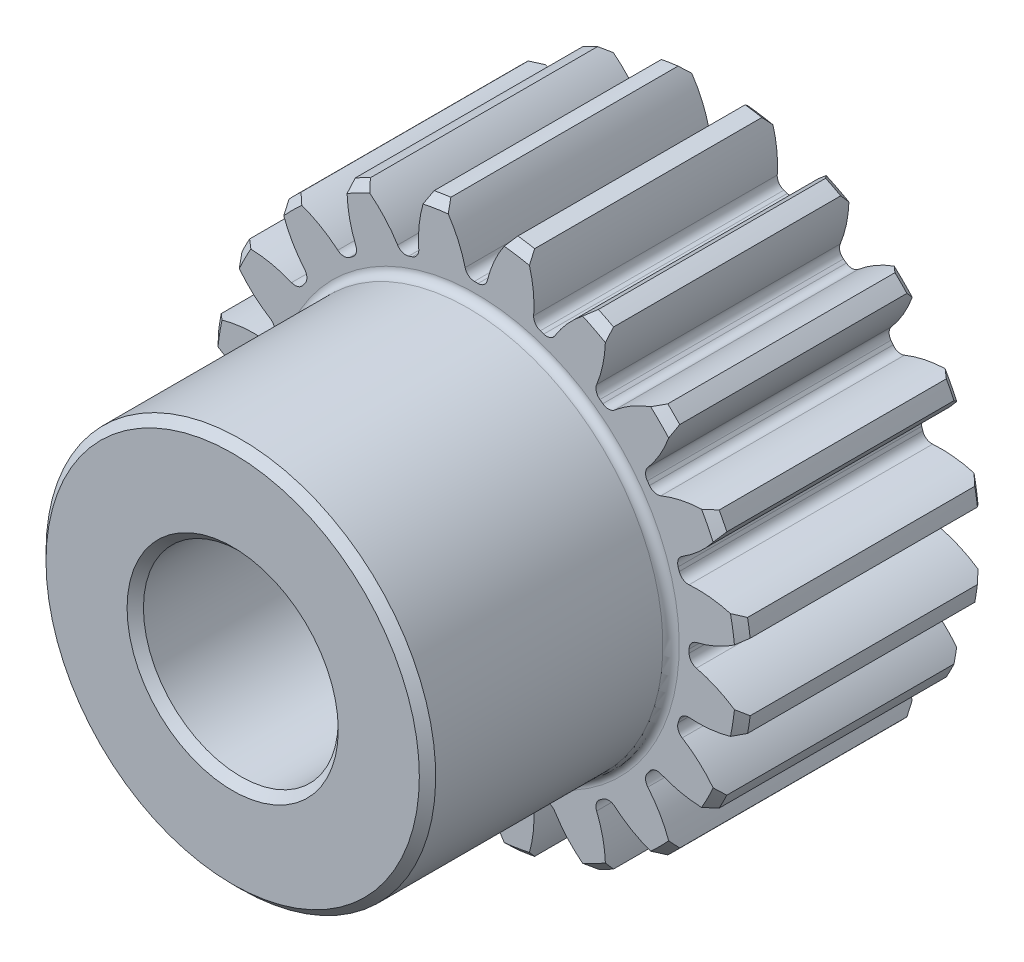
SolidWorks part; units mm, degrees
ref_plane "Front Plane" through (0, 0, 0) normal (0, 0, 1) x (1, 0, 0)
ref_plane "Top Plane" through (0, 0, 0) normal (0, 1, 0) x (1, 0, 0)
ref_plane "Right Plane" through (0, 0, 0) normal (1, 0, 0) x (0, 0, -1)
sketch "Sketch1" plane through (0, 0, 0) normal (0, 0, 1) x (1, 0, 0)
  line L0 (0, 0) -> (0, 10) construction
  line L1 (-3.2139, 11.1698) -> (3.2139, 8.8302) construction
  circle A0 centre (0, 0) radius 8.75 construction
  circle A1 centre (0, 0) radius 11 construction
  circle A2 centre (0, 0) radius 10 construction
  circle A3 centre (0, 0) radius 9.3969 construction
  circle A4 centre (0, 0) radius 8 construction
  circle A5 centre (0, 0) radius 4 construction
  point P8 (0.5, 0)
  point P13 (10, 0)
  dimension "OD" = 22
  dimension "Root Diameter" = 17.5
  dimension "Gear Pitch Diameter" = 20
  dimension "Base Diameter" = 18.7939
  dimension "Hub Diameter" = 16
  dimension "For Shaft Diameter" = 8
  dimension "Pressure Angle" = 20
  dimension "Number of Teeth" = 20
  dimension "Module" = 1
sketch "Sketch2" plane through (0, 0, 0) normal (1, 0, 0) x (0, 0, -1)
  line L0 (-10, 0) -> (10, 0) construction
  line L1 (10, 11) -> (10, -11) construction
  line L2 (0, -8) -> (-10, -8) construction
  line L3 (-10, 11) -> (10, 11) construction
  line L8 (-10, -8) -> (-10, 8) construction
  point P4 (0, 11)
  point P5 (-5, 0)
  dimension "Overall Width" = 20
  dimension "Hub Width" = 10
  dimension "Approx Set Screw Positon" = 5
  dimension "Face Width" = 10
sketch "Sketch3" plane through (0, 0, 0) normal (0, 0, 1) x (1, 0, 0)
  circle A0 centre (0, 0) radius 11
  circle A1 centre (0, 0) radius 11 construction
extrude "Boss-Extrude1" add sketch "Sketch3" against normal up to vertex (10 mm away) and the other way up to vertex (10 mm away) up to point (0, 0, -10) other way up to point (0, 0, 10)
sketch "Sketch5" plane through (0, 0, 0) normal (1, 0, 0) x (0, 0, -1)
  line L1 (0, 8) -> (-10, 8)
  line L2 (0, 8) -> (0, 11)
  line L3 (0, 11) -> (-10, 11)
  line L4 (-10, 8) -> (-10, 11)
  line L5 (-10, 0) -> (10, 0)
  line L6 (-10, 0) -> (-10, 4)
  line L7 (-10, 4) -> (10, 4)
  line L8 (10, 0) -> (10, 4)
  point P5 (0, 8)
  point P12 (0, 4)
revolve "Cut-Revolve1" cut sketch "Sketch5" angle 360 about L0
fillet "Fillet2" radius 0.3355 1 edges at (0, -8, 0)
chamfer "Chamfer1" distance 0.3355 angle 45 5 edges at (0, -4, -10) (0, -11, 0) (11, 0, -10) (0, -4, 10) (0, -8, 10)
sketch "Sketch4" plane through (0, 0, 0) normal (0, 0, 1) x (1, 0, 0)
  line L0 (8.7412, 0.3927) -> (8.7412, -0.3927)
  arc A3 (10.9135, 1.3768) -> (10.9135, -1.3768) centre (0, 0) cw
  circle A4 centre (0, 0) radius 11 construction
  arc A5 (8.7412, 0.3927) -> (10.9135, 1.3768) centre (7.8741, 5.1963) ccw
  circle A8 centre (0, 0) radius 8.75 construction
  arc A9 (8.7412, -0.3927) -> (10.9135, -1.3768) centre (7.8741, -5.1963) cw
  spline S0 degree 4 poles (9.3779, 0.5976) (9.3805, 0.5978) (9.3877, 0.5984) (9.4012, 0.6001) (9.4233, 0.6033) (9.4513, 0.6083) (9.4874, 0.6157) (9.5298, 0.6256) (9.5761, 0.6379) (9.6264, 0.6526) (9.6763, 0.6685) (9.7258, 0.6855) (9.775, 0.7034) (9.8343, 0.7264) (9.9051, 0.7556) (9.9872, 0.7922) (10.0797, 0.8366) (10.1732, 0.8848) (10.2645, 0.9348) (10.3559, 0.9882) (10.4438, 1.0418) (10.5341, 1.1004) (10.6171, 1.156) (10.709, 1.2214) (10.7829, 1.2752) (10.8792, 1.3494) (10.9357, 1.3943) (11.0014, 1.4479) (11.0304, 1.4723) (11.0482, 1.4873) knots 0 0 0 0 0 0.005377 0.015084 0.028532 0.04661 0.064855 0.092111 0.119476 0.146842 0.174209 0.201575 0.228941 0.256307 0.307035 0.361767 0.4165 0.471232 0.525964 0.580697 0.635429 0.690161 0.744894 0.799626 0.854358 0.909091 0.954545 1 1 1 1 1 construction
  spline S1 degree 4 poles (9.3779, 0.5976) (9.3805, 0.5978) (9.3877, 0.5984) (9.4012, 0.6001) (9.4233, 0.6033) (9.4513, 0.6083) (9.4874, 0.6157) (9.5298, 0.6256) (9.5761, 0.6379) (9.6264, 0.6526) (9.6763, 0.6685) (9.7258, 0.6855) (9.775, 0.7034) (9.8343, 0.7264) (9.9051, 0.7556) (9.9872, 0.7922) (10.0797, 0.8366) (10.1732, 0.8848) (10.2645, 0.9348) (10.3559, 0.9882) (10.4438, 1.0418) (10.5341, 1.1004) (10.6171, 1.156) (10.709, 1.2214) (10.7829, 1.2752) (10.8583, 1.3333) (10.8949, 1.362) (10.9135, 1.3768) knots 0 0 0 0 0 0.005377 0.015084 0.028532 0.04661 0.064855 0.092111 0.119476 0.146842 0.174209 0.201575 0.228941 0.256307 0.307035 0.361767 0.4165 0.471232 0.525964 0.580697 0.635429 0.690161 0.744894 0.799626 0.854358 0.909091 0.909091 0.909091 0.909091 0.909091 construction
  spline S2 degree 4 poles (9.3779, -0.5976) (9.3805, -0.5978) (9.3877, -0.5984) (9.4012, -0.6001) (9.4233, -0.6033) (9.4513, -0.6083) (9.4874, -0.6157) (9.5298, -0.6256) (9.5761, -0.6379) (9.6264, -0.6526) (9.6763, -0.6685) (9.7258, -0.6855) (9.775, -0.7034) (9.8343, -0.7264) (9.9051, -0.7556) (9.9872, -0.7922) (10.0797, -0.8366) (10.1732, -0.8848) (10.2645, -0.9348) (10.3559, -0.9882) (10.4438, -1.0418) (10.5341, -1.1004) (10.6171, -1.156) (10.709, -1.2214) (10.7829, -1.2752) (10.8792, -1.3494) (10.9357, -1.3943) (11.0014, -1.4479) (11.0304, -1.4723) (11.0482, -1.4873) knots 0 0 0 0 0 0.005377 0.015084 0.028532 0.04661 0.064855 0.092111 0.119476 0.146842 0.174209 0.201575 0.228941 0.256307 0.307035 0.361767 0.4165 0.471232 0.525964 0.580697 0.635429 0.690161 0.744894 0.799626 0.854358 0.909091 0.954545 1 1 1 1 1 construction
  spline S3 degree 4 poles (9.3779, -0.5976) (9.3805, -0.5978) (9.3877, -0.5984) (9.4012, -0.6001) (9.4233, -0.6033) (9.4513, -0.6083) (9.4874, -0.6157) (9.5298, -0.6256) (9.5761, -0.6379) (9.6264, -0.6526) (9.6763, -0.6685) (9.7258, -0.6855) (9.775, -0.7034) (9.8343, -0.7264) (9.9051, -0.7556) (9.9872, -0.7922) (10.0797, -0.8366) (10.1732, -0.8848) (10.2645, -0.9348) (10.3559, -0.9882) (10.4438, -1.0418) (10.5341, -1.1004) (10.6171, -1.156) (10.709, -1.2214) (10.7829, -1.2752) (10.8583, -1.3333) (10.8949, -1.362) (10.9135, -1.3768) knots 0 0 0 0 0 0.005377 0.015084 0.028532 0.04661 0.064855 0.092111 0.119476 0.146842 0.174209 0.201575 0.228941 0.256307 0.307035 0.361767 0.4165 0.471232 0.525964 0.580697 0.635429 0.690161 0.744894 0.799626 0.854358 0.909091 0.909091 0.909091 0.909091 0.909091 construction
  dimension "D1" = 0.7854
extrude "Cut-Extrude1" cut sketch "Sketch4" against normal through all both and the other way through all
fillet "Fillet1" radius 0.3927 2 edges at (8.7412, 0.3927, -5) (8.7412, -0.3927, -5)
pattern_circular "CirPattern1" count 20 over 360 about axis through (0, 0, 10) along (0, 0, -1) of "Cut-Extrude1", "Fillet1"
equation "\"Number of Teeth\"= 20"
equation "\"Module\"= 1"
equation "\"Diametral Pitch\"= 1 / \"Module\""
equation "\"Dedendum\"= 1.25 / \"Diametral Pitch\""
equation "\"Pitch Diameter\"= \"Module\" * \"Number of Teeth\""
equation "\"Root Diameter\"= \"Pitch Diameter\" - ( 2 * \"Dedendum\" )"
equation "\"Root Diameter@Sketch1\"=\"Root Diameter\""
equation "\"OD@Sketch1\" = \"Outside Diameter\""
equation "\"D1@CirPattern1\"=\"Number of Teeth\""
equation "\"Pressure Angle\"=20"
equation "\"Base Diameter\"= \"Pitch Diameter\" * cos ( \"Pressure Angle\" )"
equation "\"Outside Diameter\"= ( \"Number of Teeth\" + 2 ) / \"Diametral Pitch\""
equation "\"Pitch Angle\"= 360deg / \"Number of Teeth\""
equation "\"Alpha\"= sqr ( \"Pitch Diameter\" ^ 2 - \"Base Diameter\" ^ 2 ) / \"Base Diameter\" * 180 / PI - \"Pressure Angle\""
equation "\"Beta\"= ( \"Pitch Angle\" / 4 - \"Alpha\" )"
equation "\"Phi\"= sqr ( ( \"Outside Diameter\" / 2 ) ^ 2 - ( \"Base Diameter\" / 2 ) ^ 2 ) / ( \"Base Diameter\" / 2 )"
equation "\"Addendum\"= 1 / \"Diametral Pitch\""
equation "\"WorkingDepth\"= 2 / \"Diametral Pitch\""
equation "\"WholeDepth\"= 2.25 / \"Diametral Pitch\""
equation "\"Clearance\"= 0.25 / \"Diametral Pitch\""
equation "\"ToothThickness\"= ( pi * 2 ) / \"Diametral Pitch\""
equation "\"CircularPitch\"= pi / \"Diametral Pitch\""
equation "\"Number of Teeth@Sketch1\"=\"Number of Teeth\""
equation "\"Module@Sketch1\"=\"Module\""
equation "\"Pressure Angle@Sketch1\"=\"Pressure Angle\""
equation "\"Gear Pitch Diameter@Sketch1\"=\"Pitch Diameter\""
equation "\"Base Diameter@Sketch1\"=\"Base Diameter\""
equation "\"Fillet\"= \"Clearance\" * cos ( \"Pressure Angle\" ) * tan ( ( 90 + \"Pressure Angle\" ) / 2 )"
equation "\"D1@Fillet2\"=\"Fillet\""
equation "\"Approx Set Screw Positon@Sketch2\" = \"Hub Width@Sketch2\" / 2"
equation "\"D2\"= \"Fillet\" * 2"
equation "\"D1@Chamfer1\"=\"Fillet\""
equation "\"D1@Sketch4\"=\"CircularPitch\"*0.25"
equation "\"D1@Fillet1\"=\"CircularPitch\"*0.125"
